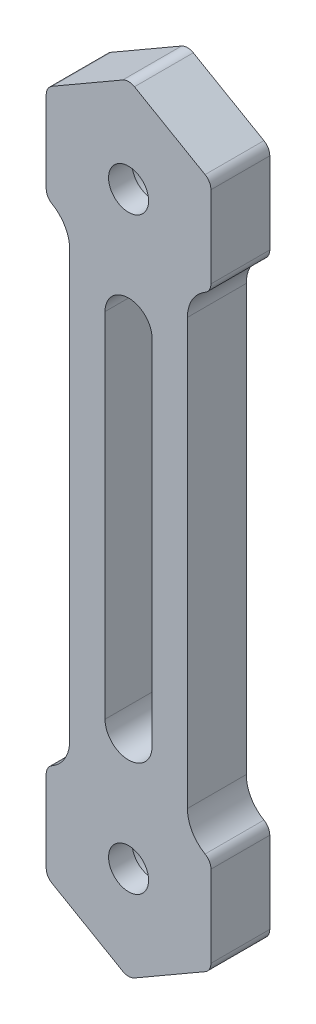
SolidWorks part; units mm, degrees
material "A2017"
ref_plane "正面" through (0, 0, 0) normal (0, 0, 1) x (1, 0, 0)
ref_plane "平面" through (0, 0, 0) normal (0, 1, 0) x (1, 0, 0)
ref_plane "右側面" through (0, 0, 0) normal (1, 0, 0) x (0, 0, -1)
sketch "ｽｹｯﾁ1" plane through (0, 0, 0) normal (0, 0, 1) x (1, 0, 0)
  line L0 (0, 0) -> (9.0749, 0) construction
  line L1 (0, 25) -> (0, 0) construction
  line L2 (0, -16.9171) -> (7, -20.9585)
  line L3 (7, 20.9585) -> (7, 29.0415)
  line L4 (7, 29.0415) -> (0, 33.0829)
  line L5 (0, 33.0829) -> (-7, 29.0415)
  line L6 (-7, 29.0415) -> (-7, 20.9585)
  line L7 (-7, 20.9585) -> (0, 16.9171)
  line L8 (0, 16.9171) -> (7, 20.9585)
  line L9 (-7, -20.9585) -> (0, -16.9171)
  line L10 (-7, -29.0415) -> (-7, -20.9585)
  line L11 (0, -33.0829) -> (-7, -29.0415)
  line L12 (7, -29.0415) -> (0, -33.0829)
  line L13 (7, -20.9585) -> (7, -29.0415)
  circle A0 centre (0, 25) radius 3
  circle A1 centre (0, -25) radius 3
  circle A2 centre (0, 25) radius 7 construction
  circle A3 centre (0, -25) radius 7 construction
  dimension "D1" = 6
  dimension "D2" = 50
  dimension "D3" = 14
extrude "ﾎﾞｽ - 押し出し1" add sketch "ｽｹｯﾁ1" along normal mid plane 5
sketch "ｽｹｯﾁ2" plane through (0, 0, 2.5) normal (0, 0, 1) x (1, 0, 0)
  line L0 (-7, 20.9585) -> (0, 16.9171) construction
  line L1 (5, -19.8038) -> (-5, -19.8038)
  line L2 (5, -19.8038) -> (5, 19.8038)
  line L3 (5, 19.8038) -> (-5, 19.8038)
  line L4 (-5, -19.8038) -> (-5, 19.8038)
  line L5 (5, -19.8038) -> (-5, 19.8038) construction
  line L6 (5, 19.8038) -> (-5, -19.8038) construction
  point P0 (0, 0)
  dimension "D1" = 10
extrude "ﾎﾞｽ - 押し出し2" add sketch "ｽｹｯﾁ2" against normal up to surface (5 mm away) up to face at (0, 25, -2.5)
fillet "ﾌｨﾚｯﾄ1" radius 3 4 edges at (5, -19.8038, 0) (-5, 19.8038, 0) (-5, -19.8038, 0) (5, 19.8038, 0)
fillet "ﾌｨﾚｯﾄ2" radius 1 10 edges at (-7, 20.9585, 0) (-7, 29.0415, 0) (0, 33.0829, 0) (7, 29.0415, 0) (7, 20.9585, 0) (7, -29.0415, 0) (0, -33.0829, 0) (-7, -29.0415, 0) (-7, -20.9585, 0) (7, -20.9585, 0)
sketch "ｽｹｯﾁ3" plane through (0, 0, -2.5) normal (0, 0, -1) x (-1, 0, 0)
  line L0 (0, -15) -> (0, 15) construction
  line L1 (-2, -15) -> (-2, 15)
  line L2 (2, -15) -> (2, 15)
  arc A0 (-2, -15) -> (2, -15) centre (0, -15) ccw
  arc A1 (2, 15) -> (-2, 15) centre (0, 15) ccw
  point P2 (0, 0)
  dimension "D1" = 4
  dimension "D2" = 30
extrude "ｶｯﾄ - 押し出し1" cut sketch "ｽｹｯﾁ3" against normal up to surface (5 mm away) up to face at (0, 0, 2.5)
sketch "ｽｹｯﾁ5" plane through (0, 0, 2.5) normal (0, 0, 1) x (1, 0, 0)
  circle A0 centre (0, -25) radius 3 construction
  circle A1 centre (0, 25) radius 3 construction
  circle A2 centre (0, -25) radius 3
  circle A3 centre (0, 25) radius 3
extrude "ﾎﾞｽ - 押し出し3" add sketch "ｽｹｯﾁ5" against normal blind 2
hole_wizard "M3 すきま穴1" positions "ｽｹｯﾁ6" profile "ｽｹｯﾁ7" hole size "M3" standard "JIS" end condition through all
sketch "ｽｹｯﾁ6" plane through (0, 0, 0.5) normal (0, 0, -1) x (-1, 0, 0)
  point P0 (0, 25)
  point P3 (0, -25)
sketch "ｽｹｯﾁ7" plane through (0, 25, 0.5) normal (1, 0, 0) x (0, 1, 0)
  line L0 (0, 0) -> (0, 2)
  line L1 (0, 2) -> (1.7, 2)
  line L2 (1.7, 2) -> (1.7, 0)
  line L5 (1.7, 0) -> (0, 0)
  line L11 (0, -6.35) -> (0, 107.95) construction
  dimension "通し穴の直径" = 3.4
  dimension "通し穴の深さ" = 2
